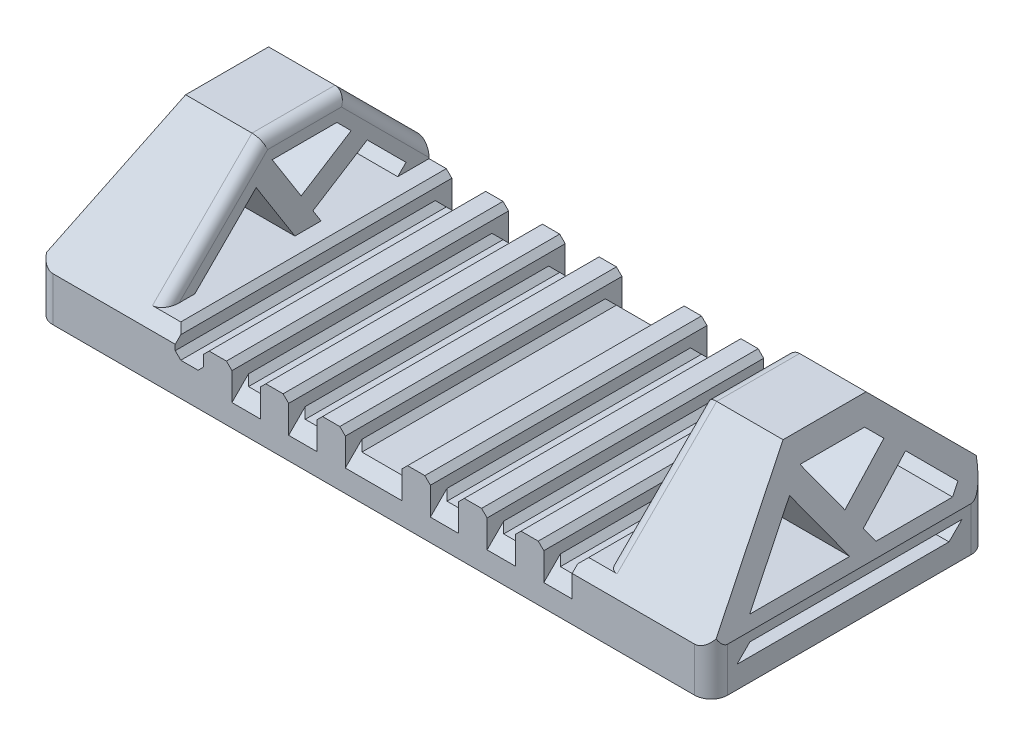
SolidWorks part; units mm, degrees
ref_plane "Front Plane" through (0, 0, 0) normal (0, 0, 1) x (1, 0, 0)
ref_plane "Top Plane" through (0, 0, 0) normal (0, 1, 0) x (1, 0, 0)
ref_plane "Right Plane" through (0, 0, 0) normal (1, 0, 0) x (0, 0, -1)
sketch "Sketch1" plane through (0, 0, 0) normal (0, 0, 1) x (1, 0, 0)
  line L0 (0, 0) -> (134, 0)
  line L1 (0, 0) -> (0, 10)
  line L2 (0, 10) -> (134, 10)
  line L3 (134, 10) -> (134, 0)
  line L4 (67, 10) -> (26, 10)
  line L5 (26, 10) -> (108, 10)
  line L6 (26, 10) -> (26, 28)
  line L8 (26, 28) -> (0, 28)
  line L9 (26, 28) -> (26, 10)
  line L10 (26, 10) -> (0, 10)
  line L11 (0, 28) -> (0, 10)
  line L12 (108, 10) -> (134, 10)
  line L13 (108, 10) -> (108, 28)
  line L14 (108, 28) -> (134, 28)
  line L15 (134, 10) -> (134, 28)
extrude "Boss-Extrude1" add sketch "Sketch1" along normal blind 50 contours L8 L11 L2 L6 | L3 L2 L1 L0 | L2 L15 L14 L13
sketch "Sketch4" plane through (0, 10, 0) normal (0, 1, 0) x (1, 0, 0)
  line L0 (67, 0) -> (67, -50)
  line L1 (26, 0) -> (108, 0) construction
  line L2 (26, -50) -> (108, -50) construction
  line L4 (26, 0) -> (67, 0)
  line L5 (26, 0) -> (26, -50)
  line L6 (26, -50) -> (67, -50)
  line L7 (67, 0) -> (67, -50)
  line L8 (67, -50) -> (108, -50)
  line L9 (67, -50) -> (67, 0)
  line L10 (67, 0) -> (108, 0)
  line L11 (108, -50) -> (108, 0)
  line L12 (108, 0) -> (87.5, 0)
  line L13 (108, 0) -> (108, -50)
  line L14 (108, -50) -> (87.5, -50)
  line L15 (87.5, 0) -> (87.5, -50)
  line L16 (46.5, -50) -> (67, -50)
  line L17 (46.5, -50) -> (46.5, 0)
  line L18 (46.5, 0) -> (67, 0)
  line L19 (67, -50) -> (67, 0)
  line L20 (26, 0) -> (46.5, 0)
  line L21 (26, 0) -> (26, -50)
  line L22 (26, -50) -> (46.5, -50)
  line L23 (46.5, 0) -> (46.5, -50)
  line L24 (36.25, -50) -> (46.5, -50)
  line L25 (36.25, -50) -> (36.25, 0)
  line L26 (36.25, 0) -> (46.5, 0)
  line L27 (46.5, -50) -> (46.5, 0)
  line L28 (56.75, -50) -> (67, -50)
  line L29 (56.75, -50) -> (56.75, 0)
  line L30 (56.75, 0) -> (67, 0)
  line L31 (67, -50) -> (67, 0)
  line L32 (67, -50) -> (87.5, -50)
  line L33 (67, -50) -> (67, 0)
  line L34 (67, 0) -> (87.5, 0)
  line L35 (87.5, -50) -> (87.5, 0)
  line L36 (77.25, 0) -> (87.5, 0)
  line L37 (77.25, 0) -> (77.25, -50)
  line L38 (77.25, -50) -> (87.5, -50)
  line L39 (87.5, 0) -> (87.5, -50)
  line L40 (97.75, -50) -> (108, -50)
  line L41 (97.75, -50) -> (97.75, 0)
  line L42 (97.75, 0) -> (108, 0)
  line L43 (108, -50) -> (108, 0)
  line L44 (26, 0) -> (36.25, 0)
  line L45 (26, 0) -> (26, -50)
  line L46 (26, -50) -> (36.25, -50)
  line L47 (36.25, 0) -> (36.25, -50)
  line L48 (31.125, -50) -> (36.25, -50)
  line L49 (31.125, -50) -> (31.125, 0)
  line L50 (31.125, 0) -> (36.25, 0)
  line L51 (36.25, -50) -> (36.25, 0)
  line L52 (36.25, 0) -> (41.375, 0)
  line L53 (36.25, 0) -> (36.25, -50)
  line L54 (36.25, -50) -> (41.375, -50)
  line L55 (41.375, 0) -> (41.375, -50)
  line L56 (46.5, -50) -> (56.75, -50)
  line L57 (46.5, -50) -> (46.5, 0)
  line L58 (46.5, 0) -> (56.75, 0)
  line L59 (56.75, -50) -> (56.75, 0)
  line L60 (51.625, 0) -> (61.875, 0)
  line L61 (51.625, 0) -> (51.625, -50)
  line L62 (51.625, -50) -> (61.875, -50)
  line L63 (61.875, 0) -> (61.875, -50)
  line L64 (67, 0) -> (77.25, 0)
  line L65 (67, 0) -> (67, -50)
  line L66 (67, -50) -> (77.25, -50)
  line L67 (77.25, 0) -> (77.25, -50)
  line L68 (72.125, -50) -> (77.25, -50)
  line L69 (72.125, -50) -> (72.125, 0)
  line L70 (72.125, 0) -> (77.25, 0)
  line L71 (77.25, -50) -> (77.25, 0)
  line L72 (77.25, -50) -> (87.5, -50)
  line L73 (77.25, -50) -> (77.25, 0)
  line L74 (77.25, 0) -> (87.5, 0)
  line L75 (87.5, -50) -> (87.5, 0)
  line L76 (82.375, 0) -> (87.5, 0)
  line L77 (82.375, 0) -> (82.375, -50)
  line L78 (82.375, -50) -> (87.5, -50)
  line L79 (87.5, 0) -> (87.5, -50)
  line L80 (87.5, -50) -> (97.75, -50)
  line L81 (87.5, -50) -> (87.5, 0)
  line L82 (87.5, 0) -> (97.75, 0)
  line L83 (97.75, -50) -> (97.75, 0)
  line L84 (92.625, 0) -> (97.75, 0)
  line L85 (92.625, 0) -> (92.625, -50)
  line L86 (92.625, -50) -> (97.75, -50)
  line L87 (97.75, 0) -> (97.75, -50)
  line L88 (97.75, -50) -> (108, -50)
  line L89 (97.75, -50) -> (97.75, 0)
  line L90 (97.75, 0) -> (108, 0)
  line L91 (108, -50) -> (108, 0)
  line L92 (102.875, 0) -> (108, 0)
  line L93 (102.875, 0) -> (102.875, -50)
  line L94 (102.875, -50) -> (108, -50)
  line L95 (108, 0) -> (108, -50)
  line M1 (108, 0) -> (26, 0)
  line M3 (26, -50) -> (108, -50)
extrude "Cut-Extrude3" cut sketch "Sketch4" against normal blind 4 contours L49 L46 L25 L20 | L93 L90 L41 L14 | L4 L55 L24 L17 | L85 L82 L15 L8 | L18 L61 L56 L29 | L77 L74 L37 L32 | L63 L28 L0 M1 | L69 L64 L0 M3
chamfer "Chamfer1" distance 2 angle 45 13 edges at (33.6875, 6, 0) (43.9375, 6, 0) (43.9375, 6, 50) (54.1875, 6, 0) (54.1875, 6, 50) (67, 6, 0) (67, 6, 50) (79.8125, 6, 0) (79.8125, 6, 50) (90.0625, 6, 0) (90.0625, 6, 50) (100.3125, 6, 0) (100.3125, 6, 50)
chamfer "Chamfer2" distance 1 angle 45 14 edges at (102.875, 10, 25) (97.75, 10, 25) (41.375, 10, 25) (46.5, 10, 25) (92.625, 10, 25) (87.5, 10, 25) (51.625, 10, 25) (56.75, 10, 25) (31.125, 10, 25) (36.25, 10, 25) (61.875, 10, 25) (72.125, 10, 25) (82.375, 10, 25) (77.25, 10, 25)
chamfer "Chamfer3" distance 1 angle 45 2 edges at (97.75, 6, 25) (102.875, 6, 25)
chamfer "Chamfer4" distance 1 angle 45 12 edges at (31.125, 6, 26) (36.25, 6, 26) (41.375, 6, 25) (46.5, 6, 25) (51.625, 6, 25) (56.75, 6, 25) (61.875, 6, 25) (72.125, 6, 25) (77.25, 6, 25) (82.375, 6, 25) (87.5, 6, 25) (92.625, 6, 25)
chamfer "Chamfer5" distance 15 angle 45 2 edges at (13, 28, 0) (121, 28, 0)
chamfer "Chamfer6" distance 20 angle 45 2 edges at (13, 28, 50) (121, 28, 50)
sketch "Sketch5" plane through (134, 0, 0) normal (1, 0, 0) x (0, 0, -1)
  line L0 (-16.6569, 24) -> (-28.3431, 24)
  line L1 (-31.2433, 21.0999) -> (-38.3431, 14)
  line L2 (-28.3431, 24) -> (-23.118, 15.7139)
  line L3 (-6.6569, 14) -> (-6.6569, 14)
  line L4 (-6.6569, 14) -> (-11.1737, 18.5169)
  line L5 (-15, 28) -> (-30, 28)
  line L6 (-30, 28) -> (-48, 10)
  line L7 (-48, 10) -> (0, 10)
  line L8 (0, 10) -> (0, 13)
  line L9 (0, 13) -> (-15, 28)
  line L10 (-15, 28) -> (-30, 28)
  line L11 (-30, 28) -> (-48, 10)
  line L12 (-48, 10) -> (0, 10)
  line L13 (0, 10) -> (0, 13)
  line L14 (0, 13) -> (-15, 28)
  line L15 (-38.3431, 14) -> (-42.3431, 10)
  line L16 (-6.6569, 14) -> (-2.6569, 10)
  line L17 (-2.6569, 10) -> (-42.3431, 10)
  line L18 (-31.2433, 21.0999) -> (-24.2438, 10)
  line L19 (-38.3431, 14) -> (-6.6569, 14) construction
  line L20 (-31.7266, 21.8664) -> (-22.8984, 7.8664) construction
  line L21 (-28.3431, 24) -> (-38.3431, 14) construction
  line L22 (-23.118, 15.7139) -> (-14.0738, 21.417)
  line L23 (-20.9844, 12.3304) -> (-11.1737, 18.5169)
  line L24 (-20.9844, 12.3304) -> (-19.5149, 10)
  line L25 (-28.3431, 24) -> (-19.5149, 10) construction
  line L26 (-20.9844, 12.3304) -> (-11.9403, 18.0335) construction
  line L27 (-14.0738, 21.417) -> (-16.6569, 24)
  line L28 (-6.6569, 14) -> (-16.6569, 24) construction
  line L29 (-42.3431, 10) -> (-2.6569, 10)
  dimension "D3" = 4
  dimension "D4" = 4
  dimension "D1" = 0
  dimension "D2" = 4
extrude "Cut-Extrude4" cut sketch "Sketch5" against normal blind 159 contours L22 L27 L0 L2 | L18 L1 L15 L12 | L23 L24 L12 L16 L4
chamfer "Chamfer9" distance 3 angle 45 1 edges at (13, 10, 2.6569)
ref_plane "Plane1" through (67, 0, 0) normal (-1, 0, 0) x (0, 0, 1)
sketch "Sketch6" plane through (134, 0, 0) normal (1, 0, 0) x (0, 0, -1)
  line L6 (-46, 6.3431) -> (-4, 6.3431)
  line L12 (-16.6569, 24) -> (-28.3431, 24)
  line L13 (-28.3431, 24) -> (-46, 6.3431)
  line L14 (-46, 6.3431) -> (-46, 4)
  line L15 (-46, 4) -> (-4, 4)
  line L16 (-4, 4) -> (-4, 11.3431)
  line L17 (-4, 11.3431) -> (-16.6569, 24)
  line L18 (-16.6569, 24) -> (-28.3431, 24)
  line L19 (-28.3431, 24) -> (-46, 6.3431)
  line L20 (-46, 6.3431) -> (-46, 4)
  line L21 (-46, 4) -> (-4, 4)
  line L22 (-4, 4) -> (-4, 11.3431)
  line L23 (-4, 11.3431) -> (-16.6569, 24)
  dimension "D1" = 4
extrude "Cut-Extrude5" cut sketch "Sketch6" against normal blind 10 contours L21 L22 L6 L20
chamfer "Chamfer10" distance 3 angle 45 2 edges at (129, 4, 4) (129, 6.3431, 46)
mirror "Mirror1" about plane through (67, 0, 0) normal (-1, 0, 0) of "Chamfer10", "Cut-Extrude5"
sketch "Sketch7" plane through (0, 0, 50) normal (0, 0, 1) x (1, 0, 0)
  line L0 (0, 8) -> (13, 28)
  line L1 (0, 28) -> (26, 28) construction
  line L2 (13, 28) -> (0, 28)
  line L3 (0, 28) -> (0, 8)
  line L4 (121, 28) -> (134, 8)
  line L5 (108, 28) -> (134, 28) construction
  line L6 (134, 8) -> (134, 28)
  line L7 (134, 28) -> (121, 28)
extrude "Cut-Extrude6" cut sketch "Sketch7" against normal blind 94
fillet "Fillet2" radius 2 4 edges at (0, 4, 50) (0, 4, 0) (134, 4, 50) (134, 4, 0)
ref_plane "Plane2" through (67, 0, 0) normal (1, 0, 0) x (0, 0, -1)
sketch "Sketch8" plane through (26, 0, 0) normal (1, 0, 0) x (0, 0, -1)
  line L0 (-16.6569, 24) -> (-14.0738, 21.417) construction
  line L1 (-14.0738, 21.417) -> (-23.118, 15.7139) construction
  line L2 (-23.118, 15.7139) -> (-28.3431, 24) construction
  line L3 (-28.3431, 24) -> (-16.6569, 24) construction
  line L4 (-16.6569, 24) -> (-14.0738, 21.417)
  line L5 (-14.0738, 21.417) -> (-23.118, 15.7139)
  line L6 (-23.118, 15.7139) -> (-28.3431, 24)
  line L7 (-28.3431, 24) -> (-16.6569, 24)
  line L13 (-11.1737, 18.5169) -> (-4.1569, 11.5)
  line L14 (-4.1569, 11.5) -> (-5.6569, 10)
  line L15 (-5.6569, 10) -> (0, 10)
  line L16 (0, 10) -> (0, 13)
  line L17 (0, 13) -> (-15, 28)
  line L18 (-15, 28) -> (-30, 28)
  line L19 (-30, 28) -> (-48, 10)
  line L20 (-48, 10) -> (-42.3431, 10)
  line L21 (-42.3431, 10) -> (-31.2433, 21.0999)
  line L22 (-31.2433, 21.0999) -> (-24.2438, 10)
  line L23 (-24.2438, 10) -> (-19.5149, 10)
  line L24 (-19.5149, 10) -> (-20.9844, 12.3304)
  line L25 (-20.9844, 12.3304) -> (-11.1737, 18.5169)
  line L26 (-11.1737, 18.5169) -> (-4.1569, 11.5)
  line L27 (-4.1569, 11.5) -> (-5.6569, 10)
  line L28 (-5.6569, 10) -> (0, 10)
  line L29 (0, 10) -> (0, 13)
  line L30 (0, 13) -> (-15, 28)
  line L31 (-15, 28) -> (-30, 28)
  line L32 (-30, 28) -> (-48, 10)
  line L33 (-48, 10) -> (-42.3431, 10)
  line L34 (-42.3431, 10) -> (-31.2433, 21.0999)
  line L35 (-31.2433, 21.0999) -> (-24.2438, 10)
  line L36 (-24.2438, 10) -> (-19.5149, 10)
  line L37 (-19.5149, 10) -> (-20.9844, 12.3304)
  line L38 (-20.9844, 12.3304) -> (-11.1737, 18.5169)
  dimension "D1" = 0
extrude "Boss-Extrude2" add sketch "Sketch8" along normal blind 1
mirror "Mirror2" about plane through (67, 0, 0) normal (1, 0, 0) of "Boss-Extrude2"
sketch "Sketch9" plane through (0, 0, 50) normal (0, 0, 1) x (1, 0, 0)
  line L0 (0, 0) -> (6, 0)
  line L1 (134, 0) -> (128, 0)
  line L2 (132, 0) -> (134, 0) construction
  line L3 (2, 0) -> (132, 0) construction
  line L4 (128, 0) -> (128, 60.5597)
  line L5 (6, 0) -> (6, 41.5779)
  line L6 (6, 8) -> (13, 28)
  line L7 (31.125, 8) -> (2, 8) construction
  line L8 (128, 8) -> (121, 28)
  line L9 (132, 8) -> (102.875, 8) construction
  line L10 (121, 28) -> (134, 8)
  line L11 (134, 8) -> (134, 0)
  line L12 (6, 0) -> (0, 0)
  line L13 (0, 0) -> (0, 8)
  line L14 (0, 0) -> (0, 8) construction
  line L15 (0, 8) -> (13, 28)
  line M1 (31.125, 8) -> (2, 8)
  line M2 (2, 8) -> (2, 0)
  line M3 (2, 0) -> (132, 0)
  line M4 (132, 0) -> (132, 8)
  line M5 (132, 8) -> (102.875, 8)
extrude "Cut-Extrude7" cut sketch "Sketch9" against normal blind 84 contours L5 M3 M1 M2 | L15 L13 L0 L5 M2 M1 | L15 L5 L6 | L10 L8 L4 | L11 L10 L4 L1 M5 M4 | L4 M3 M4 M5
fillet "Fillet3" radius 3 4 edges at (128, 4, 0) (128, 4, 50) (6, 4, 50) (6, 4, 0)
fillet "Fillet4" radius 2 6 edges at (107, 20.5, 7.5) (107, 28, 22.5) (107, 19, 39) (27, 20.5, 7.5) (27, 28, 22.5) (27, 19, 39)
